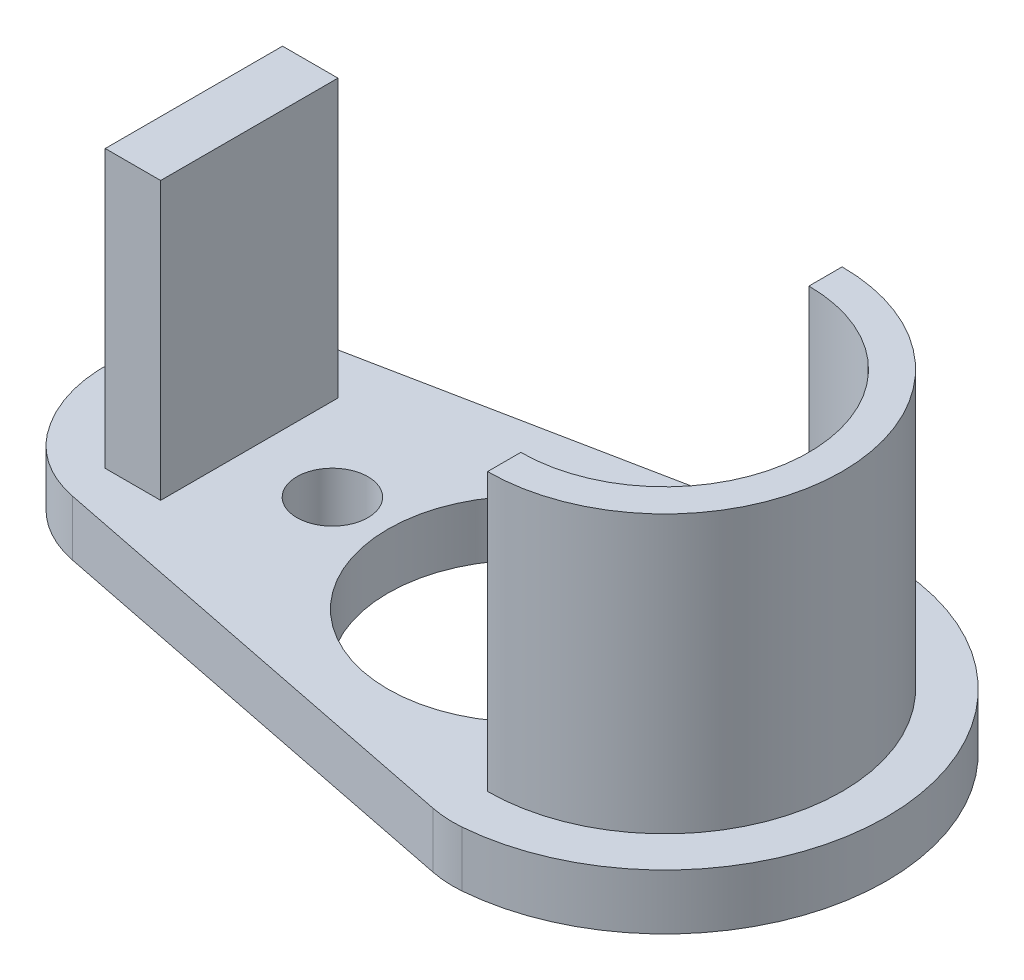
SolidWorks part; units mm, degrees
ref_plane "Front Plane" through (0, 0, 0) normal (0, 0, 1) x (1, 0, 0)
ref_plane "Top Plane" through (0, 0, 0) normal (0, 1, 0) x (1, 0, 0)
ref_plane "Right Plane" through (0, 0, 0) normal (1, 0, 0) x (0, 0, -1)
sketch "Sketch1" plane through (0, 0, 0) normal (0, 1, 0) x (1, 0, 0)
  line L0 (-0.1139, 1.9772) -> (-1.25, 1.7502)
  line L1 (-0.1139, -1.9772) -> (-1.25, -1.7502)
  line L2 (-1.25, 1.25) -> (-1.25, 1.7502)
  line L3 (-1.25, -1.25) -> (-1.25, -1.7502)
  line L4 (-1.25, -1.7502) -> (-4.1832, -1.1642)
  line L5 (-1.25, 1.7502) -> (-4.1832, 1.1642)
  line L6 (-1.25, 1.25) -> (-1.25, 1.05)
  line L7 (-1.25, -1.25) -> (-1.25, -1.05)
  line L8 (0, 1.6) -> (0, 1.3)
  line L9 (0, -1.3) -> (0, -1.6)
  line L17 (-4.25, 0.8) -> (-3.75, 0.8)
  line L18 (-4.25, 0.8) -> (-4.25, -0.8)
  line L19 (-4.25, -0.8) -> (-3.75, -0.8)
  line L20 (-3.75, 0.8) -> (-3.75, -0.8)
  circle A0 centre (-1.25, 0) radius 1.25
  circle A1 centre (-1.25, 0) radius 1.05
  arc A2 (0.1641, 1.9933) -> (0.1641, -1.9933) centre (0, 0) cw
  arc A3 (-0.1139, -1.9772) -> (0.1641, -1.9933) centre (0.0821, -0.9966) ccw
  arc A4 (-4.7783, 0.7954) -> (-4.7783, -0.7954) centre (-3.75, 0) ccw
  arc A5 (0.1641, 1.9933) -> (-0.1139, 1.9772) centre (0.0821, 0.9966) ccw
  arc A6 (-4.1832, 1.1642) -> (-4.7783, 0.7954) centre (-3.9873, 0.1835) ccw
  arc A7 (-4.1832, -1.1642) -> (-4.7783, -0.7954) centre (-3.9873, -0.1835) cw
  circle A8 centre (-3, 0) radius 0.3207
  circle A9 centre (0.5, 0) radius 0.3207
  arc A10 (0, 1.6) -> (0, -1.6) centre (0, 0) cw
  arc A11 (0, 1.3) -> (0, -1.3) centre (0, 0) cw
  point P12 (-3, 0)
  point P20 (0.5, 0)
extrude "Boss-Extrude1" add sketch "Sketch1" along normal blind 0.5 contours A2 A5 L0 L2 A0 L3 L1 A3 A11 L8 A10 L9 A9 | A7 L4 L3 A0 L2 L5 A6 A4 A8 L17 L20 L19 L18 | L8 A11 L9 A10 | L20 L17 L18 L19 region at (0.0275, 0, -1.9436) region at (-1.3017, 0, -1.5001) region at (1.5642, 0, 0) region at (-4, 0, 0)
extrude "Boss-Extrude2" add sketch "Sketch1<24>" along normal blind 3 contours L20 L17 L18 L19 | L8 A11 L9 A10 region at (1.5642, 0, 0) region at (-4, 0, 0)
sketch "Sketch1<24>" plane through (0, 0, 0) normal (0, 1, 0) x (1, 0, 0) same geometry as "Sketch1"
